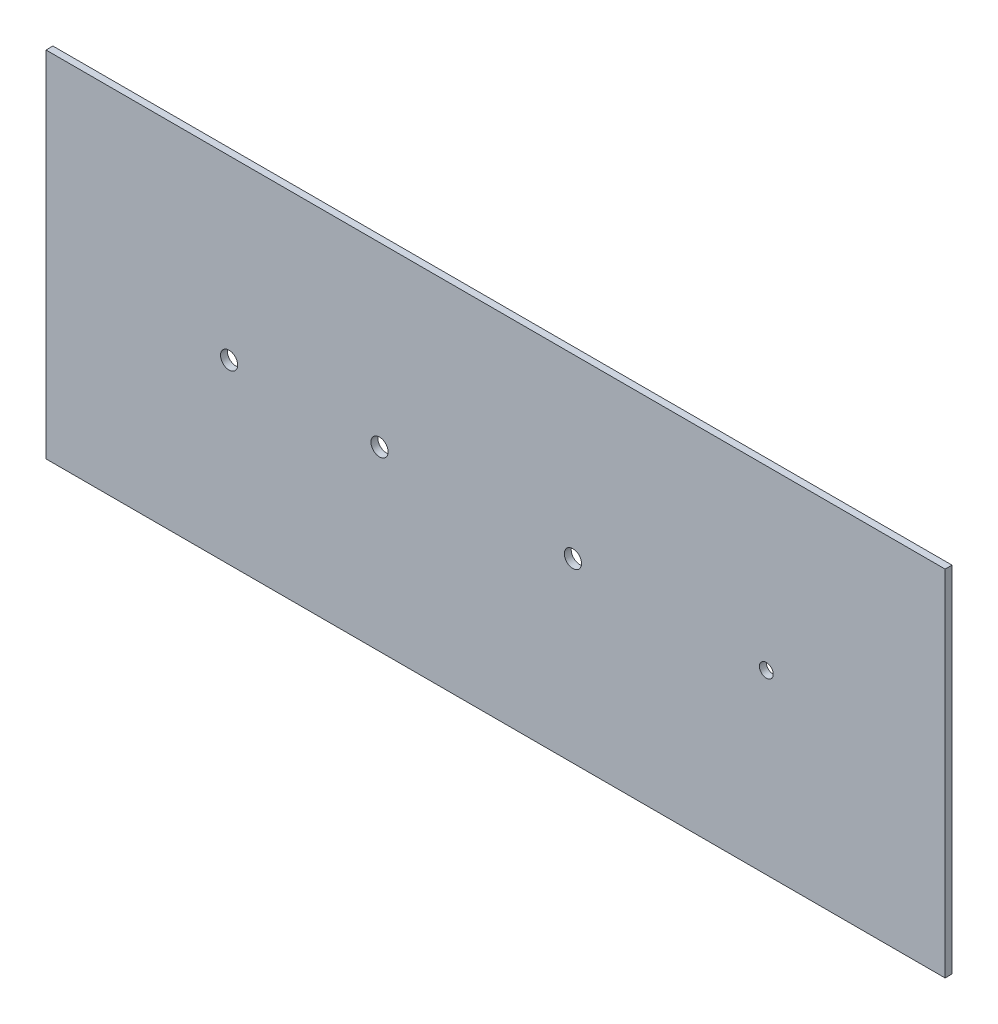
SolidWorks part; units mm, degrees
material "Сталь ШХ15 ГОСТ 801-78"
ref_plane "Plane1" through (0, 0, 0) normal (0, 0, 1) x (1, 0, 0)
ref_plane "Plane2" through (0, 0, 0) normal (0, 1, 0) x (1, 0, 0)
ref_plane "Plane3" through (0, 0, 0) normal (1, 0, 0) x (0, 0, -1)
sketch "Эскиз1" plane through (0, 0, 0) normal (0, 0, 1) x (1, 0, 0)
  line L0 (0, 51.5) -> (261.5, 51.5) construction
  line L1 (0, 0) -> (261.5, 0)
  line L2 (0, 0) -> (0, 103)
  line L3 (0, 103) -> (261.5, 103)
  line L4 (261.5, 0) -> (261.5, 103)
  circle A0 centre (22, 51.5) radius 11
  circle A1 centre (53.25, 51.5) radius 2.5
  circle A2 centre (97, 51.5) radius 2.5
  circle A3 centre (153.25, 51.5) radius 2.5
  circle A4 centre (209.5, 51.5) radius 2
  dimension "D3" = 22
  dimension "D4" = 22
  dimension "D5" = 5
  dimension "D6" = 31.25
  dimension "D9" = 52
  dimension "D1" = 103
  dimension "D2" = 56.25
  dimension "D7" = 43.75
  dimension "D8" = 56.25
extrude "Бобышка-Вытянуть1" add sketch "Эскиз1" along normal blind 2 contours L2 L0 A0 A1 A2 A3 A4 L4 L3 | L0 L2 L1 L4 A4 A3 A2 A1 A0 | A0 L0 | L0 A0 region at (132.3394, 77.6193, 0) region at (132.3394, 25.3807, 0) region at (22, 56.1685, 0) region at (22, 46.8315, 0)
